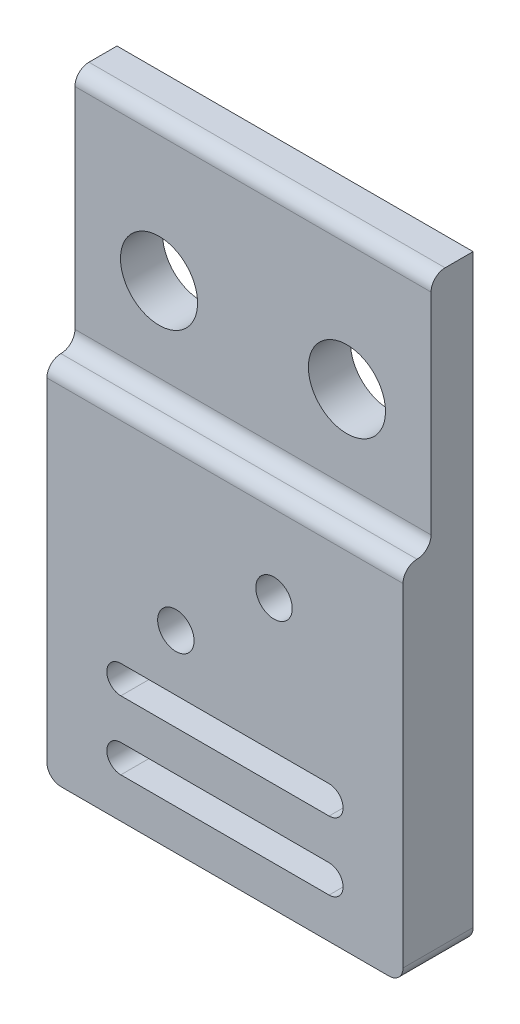
SolidWorks part; units mm, degrees
ref_plane "Front Plane" through (0, 0, 0) normal (0, 0, 1) x (1, 0, 0)
ref_plane "Top Plane" through (0, 0, 0) normal (0, 1, 0) x (1, 0, 0)
ref_plane "Right Plane" through (0, 0, 0) normal (1, 0, 0) x (0, 0, -1)
sketch "Sketch1" plane through (0, 0, 0) normal (0, 0, 1) x (1, 0, 0)
  line L0 (12.7, 0) -> (6.7, 0) construction
  line L1 (-12.7, -10) -> (12.7, -10)
  line L2 (-12.7, -10) -> (-12.7, 10)
  line L3 (-12.7, 10) -> (12.7, 10)
  line L4 (12.7, -10) -> (12.7, 10)
  line L5 (-12.7, -10) -> (12.7, 10) construction
  line L6 (-12.7, 10) -> (12.7, -10) construction
  line L7 (0, 0) -> (0, 4.9295) construction
  circle A0 centre (6.7, 0) radius 2.75
  circle A1 centre (-6.7, 0) radius 2.75
  point P0 (0, 0)
extrude "Boss-Extrude1" add sketch "Sketch1" along normal blind 3
sketch "Sketch2" plane through (0, 0, 0) normal (0, 0, 1) x (1, 0, 0)
  line L0 (-12.7, 0) -> (12.7, 0) construction
  line L1 (-12.7, 10) -> (-12.7, -10) construction
  line L2 (12.7, -10) -> (12.7, 10) construction
  line L3 (0, 0) -> (0, -7) construction
  line L4 (-12.7, -7) -> (12.7, -7)
  line L5 (12.7, -7) -> (12.7, -32.75)
  line L6 (-12.7, -7) -> (-12.7, -32.75)
  line L7 (-12.7, -32.75) -> (12.7, -32.75)
  line L8 (0, -7) -> (0, -12) construction
  line L9 (0, -12) -> (0, -15) construction
  line L10 (0, -15) -> (0, -17.5) construction
  line L11 (-7.426, -24) -> (7.426, -24) construction
  line L12 (-7.426, -23) -> (7.426, -23)
  line L13 (-7.426, -25) -> (7.426, -25)
  line L14 (0, -17.5) -> (0, -20.5) construction
  line L15 (0, -19) -> (-3.5, -19) construction
  line L16 (-7.426, -28.8808) -> (7.426, -28.8808) construction
  line L17 (-7.426, -29.8808) -> (7.426, -29.8808)
  line L18 (-7.426, -27.8808) -> (7.426, -27.8808)
  line L19 (0, -13.5) -> (3.5, -13.5) construction
  arc A0 (-7.426, -23) -> (-7.426, -25) centre (-7.426, -24) ccw
  arc A1 (7.426, -25) -> (7.426, -23) centre (7.426, -24) ccw
  arc A2 (-7.426, -29.8808) -> (-7.426, -27.8808) centre (-7.426, -28.8808) cw
  arc A3 (7.426, -27.8808) -> (7.426, -29.8808) centre (7.426, -28.8808) cw
  circle A4 centre (-3.5, -19) radius 1.3
  circle A5 centre (3.5, -13.5) radius 1.3
  point P19 (0, -24)
  point P28 (0, -28.8808)
extrude "Boss-Extrude2" add sketch "Sketch2" along normal blind 5
fillet "Fillet1" radius 1 8 edges at (-8.426, -24, 0) (0, -23, 0) (8.426, -24, 0) (0, -25, 0) (8.426, -28.8808, 0) (0, -29.8808, 0) (-8.426, -28.8808, 0) (0, -27.8808, 0)
fillet "Fillet2" radius 1 5 edges at (0, 10, 3) (0, -7, 5) (0, -7, 3) (12.7, -32.75, 2.5) (-12.7, -32.75, 2.5)
